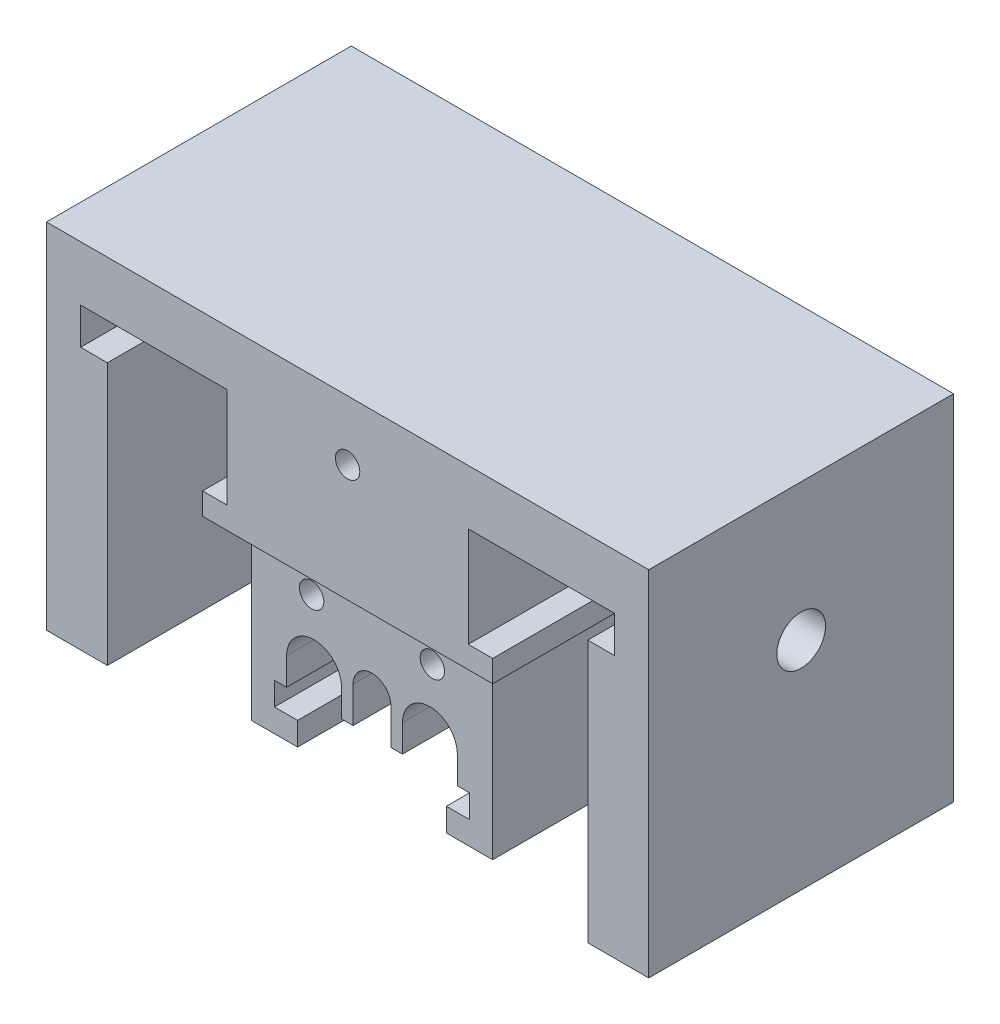
SolidWorks part; units mm, degrees
ref_plane "Front Plane" through (0, 0, 0) normal (0, 0, 1) x (1, 0, 0)
ref_plane "Top Plane" through (0, 0, 0) normal (0, 1, 0) x (1, 0, 0)
ref_plane "Right Plane" through (0, 0, 0) normal (1, 0, 0) x (0, 0, -1)
sketch "Sketch1" plane through (0, 0, 0) normal (0, 0, 1) x (1, 0, 0)
  line L0 (-21.9, 7) -> (-21.9, 10)
  line L1 (-21.9, 10) -> (-9.9, 10)
  line L2 (-9.9, 10) -> (-9.9, 1.8)
  line L3 (-9.9, -14.5) -> (9.9, -14.5)
  line L4 (9.9, -14.5) -> (9.9, 0)
  line L5 (9.9, 10) -> (21.9, 10)
  line L6 (21.9, 10) -> (21.9, 7)
  line L7 (19.7, -14.5) -> (24.7, -14.5)
  line L8 (24.7, -14.5) -> (24.7, 14.5)
  line L9 (24.7, 14.5) -> (-24.7, 14.5)
  line L14 (-24.7, 14.5) -> (-24.7, -14.5)
  line L16 (-21.9, 7) -> (-19.7, 7)
  line L17 (-19.7, 7) -> (-19.7, -14.5)
  line L18 (-19.7, -14.5) -> (-24.7, -14.5)
  line L19 (21.9, 7) -> (19.7, 7)
  line L20 (19.7, 7) -> (19.7, -14.5)
  line L22 (-9.9, 1.8) -> (-11.9, 1.8)
  line L23 (-11.9, 1.8) -> (-11.9, 0)
  line L24 (-11.9, 0) -> (-9.9, 0)
  line L25 (9.9, 1.8) -> (11.9, 1.8)
  line L26 (11.9, 1.8) -> (11.9, 0)
  line L27 (11.9, 0) -> (9.9, 0)
  line L28 (-9.9, 0) -> (-9.9, -14.5)
  line L29 (9.9, 1.8) -> (9.9, 10)
  point P9 (-24.7, 0)
  point P29 (0, -14.5)
  dimension "D1" = 19.8
  dimension "D2" = 12
  dimension "D3" = 4.5
  dimension "D4" = 4.5
  dimension "D5" = 24.5
  dimension "D6" = 5
  dimension "D7" = 2.2
  dimension "D8" = 1.8
  dimension "D9" = 14.5
  dimension "D10" = 3
  dimension "D11" = 2
extrude "Boss-Extrude1" add sketch "Sketch1" along normal blind 25
sketch "Sketch2" plane through (-24.7, 0, 0) normal (-1, 0, 0) x (0, 0, 1)
  line L0 (25, 1.8) -> (0, 1.8) construction
  line L2 (25, 1.8) -> (0, 1.8) construction
  line L3 (9.1108, 1.25) -> (17.7065, 1.25) construction
  circle A0 centre (12.5, 3.25) radius 2
  point P3 (12.5, 1.8)
  dimension "D1" = 4
  dimension "D2" = 0.55
extrude "Cut-Extrude1" cut sketch "Sketch2" against normal through all
sketch "Sketch5" plane through (0, 0, 0) normal (1, 0, 0) x (0, 0, -1)
  line L1 (-8.4008, 3.25) -> (-10.4504, 6.8)
  line L2 (-10.4504, 6.8) -> (-14.5496, 6.8)
  line L3 (-14.5496, 6.8) -> (-16.5992, 3.25)
  line L4 (-16.5992, 3.25) -> (-14.5496, -0.3)
  line L5 (-14.5496, -0.3) -> (-10.4504, -0.3)
  line L6 (-10.4504, -0.3) -> (-8.4008, 3.25)
  circle A2 centre (-12.5, 3.25) radius 3.55 construction
  dimension "D1" = 7.1
extrude "Cut-Extrude2" cut sketch "Sketch5" against normal blind 6 and the other way blind 6
sketch "Sketch6" plane through (0, 0, 0) normal (0, 0, 1) x (1, 0, 0)
  line L0 (6, 6.8) -> (-6, 6.8) construction
  line L1 (3, 6.8) -> (-3, 6.8)
  line L2 (3, 6.8) -> (3, -0.3)
  line L3 (3, -0.3) -> (-3, -0.3)
  line L4 (-3, 6.8) -> (-3, -0.3)
  line L5 (6, -0.3) -> (-6, -0.3) construction
  point P9 (0, -0.3)
  dimension "D1" = 6
extrude "Cut-Extrude3" cut sketch "Sketch6" along normal up to vertex (10.4504 mm away) up to point (-6, -0.3, 10.4504)
sketch "Sketch9" plane through (0, 0, 25) normal (0, 0, 1) x (1, 0, 0)
  line L2 (-6.1, -14.5) -> (6.1, -14.5)
  line L4 (-9.9, -14.5) -> (9.9, -14.5) construction
  line L5 (6.1, -14.5) -> (6.1, -12.6)
  line L6 (6.1, -12.6) -> (8, -12.6)
  line L7 (8, -12.6) -> (8, -10.7)
  line L8 (8, -10.7) -> (-8, -10.7)
  line L9 (-8, -10.7) -> (-8, -12.6)
  line L10 (-8, -12.6) -> (-6.1, -12.6)
  line L11 (-6.1, -12.6) -> (-6.1, -14.5)
  line L12 (-9.9, 0) -> (-9.9, -14.5) construction
  line L14 (-9.9, -12.6) -> (-8, -12.6) construction
  point P12 (0, -10.7)
  dimension "D1" = 1.9
extrude "Cut-Extrude4" cut sketch "Sketch9" against normal up to next
sketch "Sketch11" plane through (0, 0, 25) normal (0, 0, 1) x (1, 0, 0)
  line L0 (-8, -10.7) -> (-8, -12.6) construction
  line L2 (8, -12.6) -> (8, -10.7) construction
  line L3 (-7, -8.45) -> (-7, -10.7)
  line L4 (-2.5, -8.45) -> (-2.5, -10.7)
  line L5 (2.5, -8.45) -> (2.5, -10.7)
  line L6 (7, -8.45) -> (7, -10.7)
  line L7 (-7, -10.7) -> (-2.5, -10.7)
  line L8 (2.5, -10.7) -> (7, -10.7)
  line L9 (-4.75, -8.45) -> (-4.75, -6.2) construction
  line L10 (8, -10.7) -> (-8, -10.7) construction
  line L12 (-1.55, -7.75) -> (-1.55, -10.7)
  line L13 (-1.55, -10.7) -> (1.55, -10.7)
  line L14 (1.55, -7.75) -> (1.55, -10.7)
  arc A0 (-2.5, -8.45) -> (-7, -8.45) centre (-4.75, -8.45) ccw
  arc A1 (7, -8.45) -> (2.5, -8.45) centre (4.75, -8.45) ccw
  arc A2 (-1.55, -7.75) -> (1.55, -7.75) centre (0, -7.75) cw
  point P22 (0, -6.2)
  point P23 (4.75, -6.2)
  dimension "D1" = 4.5
  dimension "D2" = 1
  dimension "D3" = 1
  dimension "D4" = 3.1
extrude "Cut-Extrude5" cut sketch "Sketch11" against normal blind 23
sketch "Sketch12" plane through (0, 0, 25) normal (0, 0, 1) x (1, 0, 0)
  line L0 (6.1, -14.5) -> (9.9, -14.5) construction
  line L1 (-9.9, 0) -> (9.9, 0)
  line L2 (-9.9, 0) -> (-9.9, -14.5)
  line L3 (-9.9, -14.5) -> (9.9, -14.5)
  line L4 (9.9, 0) -> (9.9, -14.5)
  line L5 (-9.9, 0) -> (9.9, -14.5) construction
  line L6 (-9.9, -14.5) -> (9.9, 0) construction
  line L7 (-9.9, 0) -> (-9.9, -14.5) construction
  line L8 (9.9, -14.5) -> (9.9, 0) construction
  line L9 (9.9, 0) -> (11.9, 0) construction
  point P0 (0, -7.25)
extrude "Cut-Extrude6" cut sketch "Sketch12" against normal blind 2
sketch "Sketch13" plane through (0, 0, 23) normal (0, 0, 1) x (1, 0, 0)
  line L0 (0, 0) -> (0, -6.2) construction
  line L1 (9.9, 0) -> (-9.9, 0) construction
  line L2 (-9.9, -3.1) -> (0, -3.1) construction
  line L5 (-9.9, 0) -> (-9.9, -14.5) construction
  line L6 (0, -3.1) -> (9.9, -3.1) construction
  line L7 (9.9, -14.5) -> (9.9, 0) construction
  line L9 (6, 6.8) -> (-6, 6.8) construction
  line L10 (6, 6.8) -> (-6, 6.8) construction
  line L11 (6, -0.3) -> (-6, -0.3) construction
  line L12 (6, -0.3) -> (-6, -0.3) construction
  line L13 (-4.95, -3.1) -> (-4.95, -0.3) construction
  line L14 (0, 9.6) -> (0, 6.8) construction
  circle A0 centre (-4.95, -3.1) radius 1
  circle A1 centre (4.95, -3.1) radius 1
  arc A2 (1.55, -7.75) -> (-1.55, -7.75) centre (0, -7.75) ccw construction
  circle A3 centre (0, 9.6) radius 1
  point P15 (0, -3.1)
  point P20 (-4.95, -3.1)
  point P21 (4.95, -3.1)
  dimension "D1" = 2
extrude "Cut-Extrude7" cut sketch "Sketch13" against normal blind 12 and the other way blind 2
